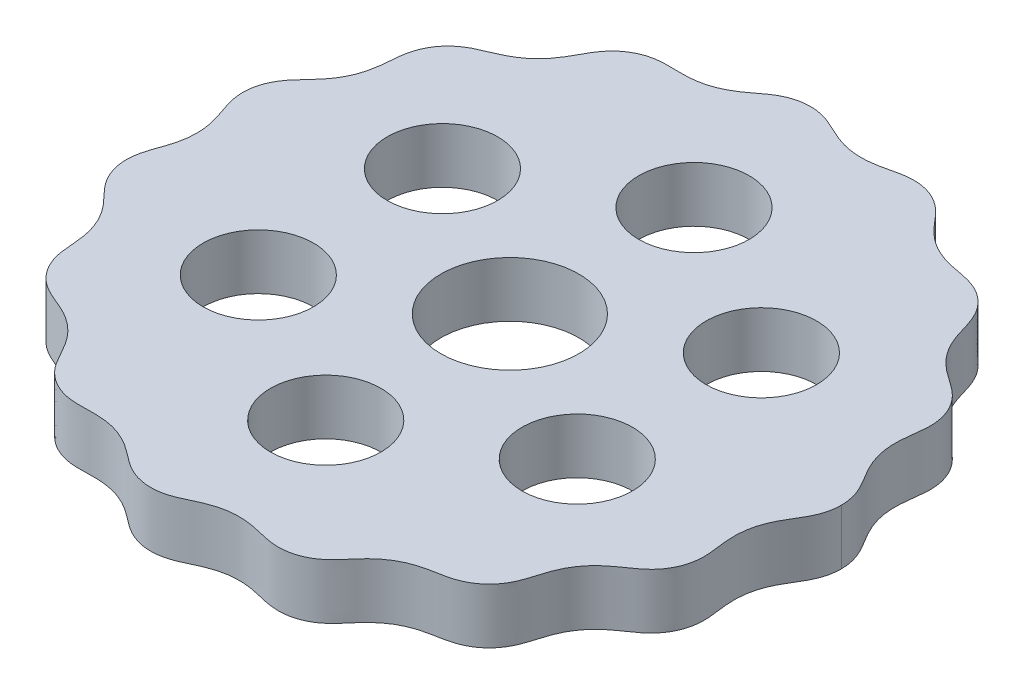
SolidWorks part; units mm, degrees
ref_plane "Front Plane" through (0, 0, 0) normal (0, 0, 1) x (1, 0, 0)
ref_plane "Top Plane" through (0, 0, 0) normal (0, 1, 0) x (1, 0, 0)
ref_plane "Right Plane" through (0, 0, 0) normal (1, 0, 0) x (0, 0, -1)
sketch "Sketch3" plane through (0, 0, 0) normal (0, 1, 0) x (1, 0, 0)
  line L0 (-55, 0) -> (55, 0) construction
  spline S2 degree 4 poles (-35, 0) (-35, -0.0358) (-35.0006, -0.1075) (-35.0034, -0.2568) (-35.0108, -0.4216) (-35.0218, -0.5882) (-35.0365, -0.7567) (-35.0593, -0.9658) (-35.104, -1.2906) (-35.1852, -1.7284) (-35.3211, -2.2743) (-35.5114, -2.8829) (-35.7441, -3.5419) (-35.9992, -4.258) (-36.256, -5.1614) (-36.3903, -6.2748) (-36.277, -7.5121) (-35.8687, -8.6952) (-35.2773, -9.6694) (-34.5543, -10.5199) (-33.7836, -11.2989) (-32.9858, -12.2016) (-32.2646, -13.303) (-31.7377, -14.5286) (-31.4262, -15.8454) (-31.2991, -17.2726) (-31.2161, -18.7053) (-30.8161, -20.1006) (-30.0732, -21.3418) (-29.1744, -22.2504) (-28.1724, -22.8961) (-27.1276, -23.3559) (-26.1086, -23.7587) (-25.0498, -24.278) (-23.9897, -24.9979) (-23.0387, -25.9222) (-22.2349, -27.0329) (-21.57, -28.2819) (-20.9001, -29.5134) (-19.9625, -30.5741) (-18.7952, -31.3663) (-17.5956, -31.8107) (-16.4147, -31.9743) (-15.2812, -31.959) (-14.2035, -31.9175) (-13.0422, -31.968) (-11.7833, -32.2012) (-10.5313, -32.6697) (-9.484, -33.2925) (-8.6483, -33.9206) (-7.824, -34.5602) (-6.9633, -35.1551) (-5.8447, -35.655) (-4.4715, -35.8938) (-3.1871, -35.8055) (-2.026, -35.4617) (-0.9923, -34.9762) (-0.0227, -34.5029) (1.0531, -34.0876) (2.2996, -33.7945) (3.6433, -33.7224) (5.0385, -33.8989) (6.246, -34.2125) (7.2644, -34.4441) (8.3052, -34.5433) (9.3521, -34.4822) (10.5168, -34.1673) (11.6593, -33.5372) (12.5907, -32.7091) (13.341, -31.8149) (14.0543, -30.9824) (14.885, -30.183) (15.9219, -29.4318) (16.9904, -28.9178) (18.0263, -28.6023) (18.918, -28.4136) (19.5788, -28.294) (20.4038, -28.1355) (21.3777, -27.8617) (22.444, -27.3351) (23.4837, -26.4602) (24.2541, -25.4059) (24.7506, -24.2626) (25.0639, -23.1466) (25.3786, -22.114) (25.8131, -21.0649) (26.4604, -19.9607) (27.3438, -18.9326) (28.3229, -18.1436) (29.2182, -17.5418) (30.0287, -16.9727) (30.7971, -16.3286) (31.5499, -15.4136) (32.138, -14.1887) (32.4089, -12.902) (32.389, -11.6377) (32.2136, -10.4744) (32.0853, -9.3852) (32.0701, -8.4106) (32.1519, -7.5639) (32.3146, -6.756) (32.5488, -5.9926) (32.8579, -5.2665) (33.2246, -4.5794) (33.5887, -3.9735) (33.9236, -3.4333) (34.2476, -2.8753) (34.5352, -2.2866) (34.722, -1.7814) (34.8335, -1.3753) (34.8947, -1.0872) (34.9248, -0.9216) (34.9499, -0.7552) (34.9676, -0.6083) (34.9796, -0.4838) (34.9875, -0.3802) (34.9925, -0.2949) (34.9973, -0.1832) (34.9994, -0.0895) (35, -0.0358) (35, 0) knots 0.07237 0.07237 0.07237 0.07237 0.07237 0.073615 0.074861 0.076106 0.077352 0.078597 0.079843 0.082334 0.087049 0.091763 0.096478 0.101193 0.107725 0.114257 0.124215 0.134174 0.144133 0.15093 0.157727 0.167143 0.176558 0.186521 0.196482 0.206428 0.216375 0.228908 0.238867 0.248826 0.258784 0.266347 0.27391 0.282559 0.291208 0.301173 0.311645 0.3216 0.331555 0.343059 0.353018 0.362977 0.372935 0.380513 0.388091 0.396475 0.404859 0.414823 0.425824 0.43578 0.440758 0.445737 0.45671 0.466668 0.476627 0.486585 0.494428 0.502271 0.510391 0.51851 0.528475 0.540003 0.54996 0.559918 0.565389 0.570861 0.580819 0.590778 0.600736 0.609095 0.617453 0.625308 0.633162 0.643126 0.655188 0.660155 0.665121 0.670088 0.675054 0.685012 0.69497 0.704929 0.714887 0.72326 0.731632 0.739222 0.746812 0.756777 0.769366 0.779036 0.78387 0.788705 0.798662 0.808621 0.81858 0.828538 0.837175 0.845812 0.853389 0.860965 0.865947 0.870929 0.877739 0.88455 0.889251 0.893953 0.898654 0.903356 0.908335 0.913314 0.914559 0.915803 0.917048 0.918293 0.919538 0.92016 0.920783 0.921405 0.922028 0.923272 0.923272 0.923272 0.923272 0.923272
  spline S3 degree 4 poles (-35, 0) (-35, 0.0358) (-35.0006, 0.1075) (-35.0034, 0.2568) (-35.0108, 0.4216) (-35.0218, 0.5882) (-35.0365, 0.7567) (-35.0593, 0.9658) (-35.104, 1.2906) (-35.1852, 1.7284) (-35.3211, 2.2743) (-35.5114, 2.8829) (-35.7441, 3.5419) (-35.9992, 4.258) (-36.256, 5.1614) (-36.3903, 6.2748) (-36.277, 7.5121) (-35.8687, 8.6952) (-35.2773, 9.6694) (-34.5543, 10.5199) (-33.7836, 11.2989) (-32.9858, 12.2016) (-32.2646, 13.303) (-31.7377, 14.5286) (-31.4262, 15.8454) (-31.2991, 17.2726) (-31.2161, 18.7053) (-30.8161, 20.1006) (-30.0732, 21.3418) (-29.1744, 22.2504) (-28.1724, 22.8961) (-27.1276, 23.3559) (-26.1086, 23.7587) (-25.0498, 24.278) (-23.9897, 24.9979) (-23.0387, 25.9222) (-22.2349, 27.0329) (-21.57, 28.2819) (-20.9001, 29.5134) (-19.9625, 30.5741) (-18.7952, 31.3663) (-17.5956, 31.8107) (-16.4147, 31.9743) (-15.2812, 31.959) (-14.2035, 31.9175) (-13.0422, 31.968) (-11.7833, 32.2012) (-10.5313, 32.6697) (-9.484, 33.2925) (-8.6483, 33.9206) (-7.824, 34.5602) (-6.9633, 35.1551) (-5.8447, 35.655) (-4.4715, 35.8938) (-3.1871, 35.8055) (-2.026, 35.4617) (-0.9923, 34.9762) (-0.0227, 34.5029) (1.0531, 34.0876) (2.2996, 33.7945) (3.6433, 33.7224) (5.0385, 33.8989) (6.246, 34.2125) (7.2644, 34.4441) (8.3052, 34.5433) (9.3521, 34.4822) (10.5168, 34.1673) (11.6593, 33.5372) (12.5907, 32.7091) (13.341, 31.8149) (14.0543, 30.9824) (14.885, 30.183) (15.9219, 29.4318) (16.9904, 28.9178) (18.0263, 28.6023) (18.918, 28.4136) (19.5788, 28.294) (20.4038, 28.1355) (21.3777, 27.8617) (22.444, 27.3351) (23.4837, 26.4602) (24.2541, 25.4059) (24.7506, 24.2626) (25.0639, 23.1466) (25.3786, 22.114) (25.8131, 21.0649) (26.4604, 19.9607) (27.3438, 18.9326) (28.3229, 18.1436) (29.2182, 17.5418) (30.0287, 16.9727) (30.7971, 16.3286) (31.5499, 15.4136) (32.138, 14.1887) (32.4089, 12.902) (32.389, 11.6377) (32.2136, 10.4744) (32.0853, 9.3852) (32.0701, 8.4106) (32.1519, 7.5639) (32.3146, 6.756) (32.5488, 5.9926) (32.8579, 5.2665) (33.2246, 4.5794) (33.5887, 3.9735) (33.9236, 3.4333) (34.2476, 2.8753) (34.5352, 2.2866) (34.722, 1.7814) (34.8335, 1.3753) (34.8947, 1.0872) (34.9248, 0.9216) (34.9499, 0.7552) (34.9676, 0.6083) (34.9796, 0.4838) (34.9875, 0.3802) (34.9925, 0.2949) (34.9973, 0.1832) (34.9994, 0.0895) (35, 0.0358) (35, 0) knots 0.07237 0.07237 0.07237 0.07237 0.07237 0.073615 0.074861 0.076106 0.077352 0.078597 0.079843 0.082334 0.087049 0.091763 0.096478 0.101193 0.107725 0.114257 0.124215 0.134174 0.144133 0.15093 0.157727 0.167143 0.176558 0.186521 0.196482 0.206428 0.216375 0.228908 0.238867 0.248826 0.258784 0.266347 0.27391 0.282559 0.291208 0.301173 0.311645 0.3216 0.331555 0.343059 0.353018 0.362977 0.372935 0.380513 0.388091 0.396475 0.404859 0.414823 0.425824 0.43578 0.440758 0.445737 0.45671 0.466668 0.476627 0.486585 0.494428 0.502271 0.510391 0.51851 0.528475 0.540003 0.54996 0.559918 0.565389 0.570861 0.580819 0.590778 0.600736 0.609095 0.617453 0.625308 0.633162 0.643126 0.655188 0.660155 0.665121 0.670088 0.675054 0.685012 0.69497 0.704929 0.714887 0.72326 0.731632 0.739222 0.746812 0.756777 0.769366 0.779036 0.78387 0.788705 0.798662 0.808621 0.81858 0.828538 0.837175 0.845812 0.853389 0.860965 0.865947 0.870929 0.877739 0.88455 0.889251 0.893953 0.898654 0.903356 0.908335 0.913314 0.914559 0.915803 0.917048 0.918293 0.919538 0.92016 0.920783 0.921405 0.922028 0.923272 0.923272 0.923272 0.923272 0.923272
extrude "Boss-Extrude1" add sketch "Sketch3" along normal blind 6
sketch "Sketch4" plane through (0, 6, 0) normal (0, 1, 0) x (1, 0, 0)
  circle A0 centre (-1, 0) radius 7.5
  circle A1 centre (-1, 0) radius 20 construction
  circle A2 centre (-1, 20) radius 6
  circle A3 centre (16.3205, 10) radius 6
  circle A4 centre (16.3205, -10) radius 6
  circle A5 centre (-1, -20) radius 6
  circle A6 centre (-18.3205, -10) radius 6
  circle A7 centre (-18.3205, 10) radius 6
  point P2 (-5.0985, 0)
  point P19 (-1, 0)
  dimension "D1" = 15
  dimension "D2" = 40
  dimension "D3" = 12
  dimension "D5" = 1
  dimension "D4" = 6
extrude "Cut-Extrude1" cut sketch "Sketch4" against normal through all
equation "\"R_SUN\"= 40"
equation "\"R_ROLL\"= 5"
equation "\"GRATIO\"= 15"
equation "\"RHO\"= 1"
